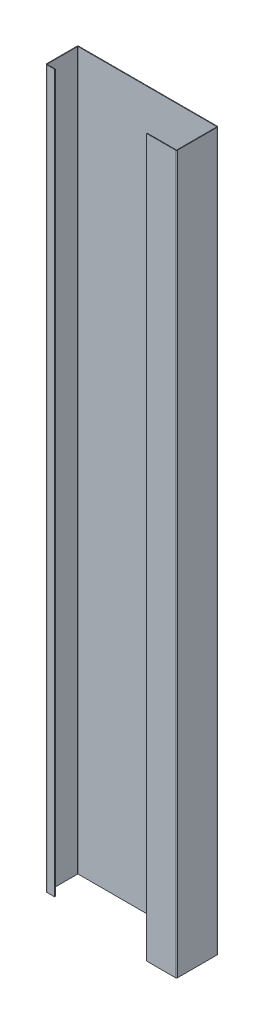
SolidWorks part; units mm, degrees
note: The reader was unsure of these and kept them because the rebuilt part matched: flange length of "Edge-Flange2", "Edge-Flange3", "Edge-Flange4", "Edge-Flange5".
ref_plane "Front Plane" through (0, 0, 0) normal (0, 0, 1) x (1, 0, 0)
ref_plane "Top Plane" through (0, 0, 0) normal (0, 1, 0) x (1, 0, 0)
ref_plane "Right Plane" through (0, 0, 0) normal (1, 0, 0) x (0, 0, -1)
sketch "Sketch1" plane through (0, 0, 0) normal (0, 0, 1) x (1, 0, 0)
  line L1 (-1138.3956, 1863.162) -> (-903.3956, 1863.162)
  line L2 (-1138.3956, 1863.162) -> (-1138.3956, 663.162)
  line L3 (-1138.3956, 663.162) -> (-903.3956, 663.162)
  line L4 (-903.3956, 1863.162) -> (-903.3956, 663.162)
  dimension "D1" = 235
  dimension "D2" = 1200
base flange "Base-Flange1" sketch "Sketch1" thickness 1 reverse thickness direction no parameters "D1"=0.7366
edge flange "Edge-Flange2" sketch "Sketch11" flange angle 90 flange length 52 flange position material inside bend radius 0.7366 thickness 1 relief rectangular parameters "D6"=10
sketch "Sketch11" plane through (-1138.3956, 0, 0) normal (-1, 0, 0) x (0, -1, 0)
  line L2 (-1863.162, 0) -> (-1863.162, 51)
  line L3 (-1863.162, 51) -> (-663.162, 51)
  line L4 (-663.162, 51) -> (-663.162, 0)
  line L11 (-1863.162, 0) -> (-663.162, 0) construction
  line L12 (-1863.162, 0) -> (-663.162, 0)
bend "EdgeBend2" bend radius 0.7366 bend angle 90 parameters "D5"=1
edge flange "Edge-Flange3" sketch "Sketch14" flange angle 90 flange length 15 flange position bend outside bend radius 0.7366 thickness 1 relief rectangular parameters "D6"=10
sketch "Sketch14" plane through (-1137.3956, 0, 51) normal (0, 0, 1) x (0, -1, 0)
  line L2 (-1863.162, 0) -> (-1863.162, 14)
  line L3 (-1863.162, 14) -> (-663.162, 14)
  line L4 (-663.162, 14) -> (-663.162, 0)
  line L7 (-663.162, 0) -> (-1863.162, 0) construction
  line L8 (-663.162, 0) -> (-1863.162, 0)
bend "EdgeBend3" bend radius 0.7366 bend angle 90 parameters "D5"=2
edge flange "Edge-Flange4" sketch "Sketch17" flange angle 90 flange length 68 flange position material inside bend radius 0.7366 thickness 1 relief rectangular parameters "D6"=10
sketch "Sketch17" plane through (-903.3956, 0, 0) normal (1, 0, 0) x (0, 1, 0)
  line L0 (663.162, 0) -> (1863.162, 0) construction
  line L1 (663.162, 0) -> (1863.162, 0)
  line L2 (663.162, 0) -> (663.162, 67)
  line L3 (663.162, 67) -> (1863.162, 67)
  line L4 (1863.162, 67) -> (1863.162, 0)
bend "EdgeBend4" bend radius 0.7366 bend angle 90 parameters "D5"=3
edge flange "Edge-Flange5" sketch "Sketch20" flange angle 90 flange length 50 flange position bend outside bend radius 0.7366 thickness 1 relief rectangular parameters "D6"=10
sketch "Sketch20" plane through (-904.3956, 0, 67) normal (0, 0, 1) x (0, 1, 0)
  line L0 (1863.162, 0) -> (663.162, 0) construction
  line L1 (1863.162, 0) -> (663.162, 0)
  line L2 (663.162, 0) -> (663.162, 49)
  line L3 (663.162, 49) -> (1863.162, 49)
  line L4 (1863.162, 49) -> (1863.162, 0)
bend "EdgeBend5" bend radius 0.7366 bend angle 90 parameters "D5"=4
sketch "Bend-Lines1" [suppressed] plane through (0, 0, 0) normal (0, 1, 0) x (1, 0, 0)
sketch "Bounding-Box1" [suppressed] plane through (0, 0, 0) normal (0, 1, 0) x (1, 0, 0)
sheet metal parameters "Sheet-Metal1" thickness 1 parameters "D1"=0.7366
flat pattern "Flat-Pattern1" [suppressed]
sketch "Bend-Lines2" plane through (0, 0, 0) normal (0, 1, 0) x (1, 0, 0)
sketch3d "Bounding-Box2" [suppressed]
  line L0 (-903.3956, 1863.162, 0) -> (-903.3956, -2141.3551, 0) construction
  line L1 (-1138.3956, 1863.162, 0) -> (-1138.3956, -2141.3551, 0) construction
  line L2 (-903.3956, 1863.162, 0) -> (-1138.3956, 1863.162, 0) construction
  line L3 (-903.3956, -2141.3551, 0) -> (-1138.3956, -2141.3551, 0) construction
sheet metal parameters "Sheet-Metal3" thickness 1 parameters "D1"=0.7366
flat pattern "Flat-Pattern1"
sketch "Bend-Lines2" plane through (0, 0, 0) normal (0, 0, 1) x (1, 0, 0)
  line L0 (-1137.6303, 1863.162) -> (-1137.6303, -2141.3551) construction
  line L1 (-1137.6303, 1863.162) -> (-1137.6303, -2141.3551) construction
sketch3d "Bounding-Box2" [suppressed]
  line L0 (-903.3956, 1863.162, 0) -> (-903.3956, -2141.3551, 0) construction
  line L1 (-1187.8649, 1863.162, 0) -> (-1187.8649, -2141.3551, 0) construction
  line L2 (-903.3956, 1863.162, 0) -> (-1187.8649, 1863.162, 0) construction
  line L3 (-903.3956, -2141.3551, 0) -> (-1187.8649, -2141.3551, 0) construction
bend of the flat pattern "Flatten-<EdgeBend2>1"
sheet metal parameters "Sheet-Metal4" thickness 1 parameters "D1"=0.7366
flat pattern "Flat-Pattern1"
sketch "Bend-Lines2" plane through (0, 0, 0) normal (0, 0, 1) x (1, 0, 0)
  line L0 (-1137.6303, 1863.162) -> (-1137.6303, -2141.3551) construction
  line L1 (-1137.6303, 1863.162) -> (-1137.6303, -2141.3551) construction
  line L2 (-1187.0995, 1863.162) -> (-1187.0995, -2141.3551) construction
  line L3 (-1187.0995, 1863.162) -> (-1187.0995, -2141.3551) construction
sketch3d "Bounding-Box2" [suppressed]
  line L0 (-903.3956, 1863.162, 0) -> (-903.3956, -2141.3551, 0) construction
  line L1 (-1201.3341, 1863.162, 0) -> (-1201.3341, -2141.3551, 0) construction
  line L2 (-903.3956, 1863.162, 0) -> (-1201.3341, 1863.162, 0) construction
  line L3 (-903.3956, -2141.3551, 0) -> (-1201.3341, -2141.3551, 0) construction
bend of the flat pattern "Flatten-<EdgeBend2>1"
bend of the flat pattern "Flatten-<EdgeBend3>1"
sheet metal parameters "Sheet-Metal5" thickness 1 parameters "D1"=0.7366
flat pattern "Flat-Pattern1"
sketch "Bend-Lines2" plane through (0, 0, 0) normal (0, 0, 1) x (1, 0, 0)
  line L0 (-1137.6303, 1863.162) -> (-1137.6303, -2141.3551) construction
  line L1 (-1137.6303, 1863.162) -> (-1137.6303, -2141.3551) construction
  line L2 (-1187.0995, 1863.162) -> (-1187.0995, -2141.3551) construction
  line L3 (-1187.0995, 1863.162) -> (-1187.0995, -2141.3551) construction
  line L4 (-904.161, -2141.3551) -> (-904.161, 1863.162) construction
  line L5 (-904.161, -2141.3551) -> (-904.161, 1863.162) construction
sketch3d "Bounding-Box2" [suppressed]
  line L0 (-836.9264, 1863.162, 0) -> (-836.9264, -2141.3551, 0) construction
  line L1 (-1201.3341, 1863.162, 0) -> (-1201.3341, -2141.3551, 0) construction
  line L2 (-836.9264, 1863.162, 0) -> (-1201.3341, 1863.162, 0) construction
  line L3 (-836.9264, -2141.3551, 0) -> (-1201.3341, -2141.3551, 0) construction
bend of the flat pattern "Flatten-<EdgeBend2>1"
bend of the flat pattern "Flatten-<EdgeBend3>1"
bend of the flat pattern "Flatten-<EdgeBend4>1"
sheet metal parameters "Sheet-Metal6" thickness 1 parameters "D1"=0.7366
flat pattern "Flat-Pattern1"
sketch "Bend-Lines2" plane through (0, 0, 0) normal (0, 0, 1) x (1, 0, 0)
  line L0 (-1137.6303, 1863.162) -> (-1137.6303, 663.162) construction
  line L1 (-1137.6303, 1863.162) -> (-1137.6303, 663.162) construction
  line L2 (-1189.8361, 1863.162) -> (-1189.8361, 663.162) construction
  line L3 (-1189.8361, 1863.162) -> (-1189.8361, 663.162) construction
  line L4 (-904.161, 663.162) -> (-904.161, 1863.162) construction
  line L5 (-904.161, 663.162) -> (-904.161, 1863.162) construction
  line L6 (-835.9552, 663.162) -> (-835.9552, 1863.162) construction
  line L7 (-835.9552, 663.162) -> (-835.9552, 1863.162) construction
sketch3d "Bounding-Box2" [suppressed]
  line L0 (-786.7205, 1863.162, 0) -> (-786.7205, 663.162, 0) construction
  line L1 (-1204.0707, 1863.162, 0) -> (-1204.0707, 663.162, 0) construction
  line L2 (-786.7205, 1863.162, 0) -> (-1204.0707, 1863.162, 0) construction
  line L3 (-786.7205, 663.162, 0) -> (-1204.0707, 663.162, 0) construction
bend of the flat pattern "Flatten-<EdgeBend2>1"
bend of the flat pattern "Flatten-<EdgeBend3>1"
bend of the flat pattern "Flatten-<EdgeBend4>1"
bend of the flat pattern "Flatten-<EdgeBend5>1"
